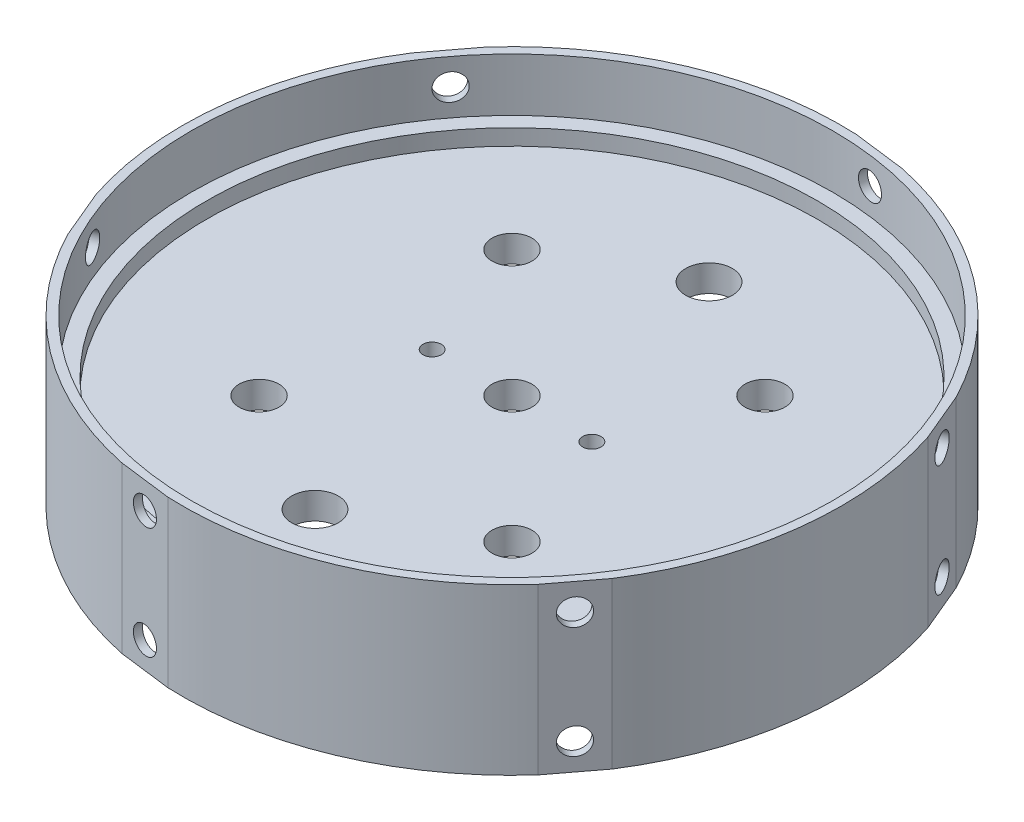
SolidWorks part; units mm, degrees
material "6061-T6 (SS)"
ref_plane "Front Plane" through (0, 0, 0) normal (0, 0, 1) x (1, 0, 0)
ref_plane "Top Plane" through (0, 0, 0) normal (0, 1, 0) x (1, 0, 0)
ref_plane "Right Plane" through (0, 0, 0) normal (1, 0, 0) x (0, 0, -1)
ref_axis "Axis1" through (0, 55, 0) along (0, -1, 0)
sketch "Sketch3" plane through (0, 0, 0) normal (0, 1, 0) x (1, 0, 0)
  circle A0 centre (0, 0) radius 78.5876
  dimension "D1" = 157.1752
extrude "Boss-Extrude1" add sketch "Sketch3" along normal blind 3.175 and the other way blind 3.175
sketch "Sketch4" plane through (0, 3.175, 0) normal (0, 1, 0) x (1, 0, 0)
  circle A0 centre (0, 0) radius 78.5876
  circle A1 centre (0, 0) radius 72.8662
  dimension "D1" = 157.1752
  dimension "D2" = 145.7325
extrude "Boss-Extrude3" add sketch "Sketch4" along normal blind 3.81
sketch "Sketch6" plane through (0, 6.985, 0) normal (0, 1, 0) x (1, 0, 0)
  circle A0 centre (0, 0) radius 78.5876
  circle A1 centre (0, 0) radius 76.454
  dimension "D1" = 157.1752
  dimension "D2" = 152.908
extrude "Boss-Extrude4" add sketch "Sketch6" along normal blind 12.7
hole_wizard "1/4 (0.25) Diameter Hole2" positions "3DSketch2" profile "Sketch7" hole size "1/4" standard "ANSI Inch" end condition up to next
sketch3d "3DSketch2"
  point P0 (-9.8633, 13.335, 77.9662)
  dimension "D1" = 6.35
sketch "Sketch7" plane through (-9.8633, 13.335, 77.9662) normal (0, 1, 0) x (0.9921, 0, 0.1255)
  line L0 (0, 0) -> (0, 185.7135)
  line L1 (0, 185.7135) -> (3.175, 185.7135)
  line L2 (3.175, 185.7135) -> (3.175, 0)
  line L5 (3.175, 0) -> (0, 0)
  line L11 (0, -6.35) -> (0, 107.95) construction
  dimension "Thru Hole Dia." = 6.35
  dimension "Thru Hole Depth" = 185.7135
pattern_circular "CirPattern2" count 6 over 360 about axis through (0, 55, 0) along (0, -1, 0) of "1/4 (0.25) Diameter Hole2"
mirror "Mirror3" about plane through (0, 0, 0) normal (0, 1, 0) of "Boss-Extrude3", "Boss-Extrude4", "1/4 (0.25) Diameter Hole2", "CirPattern2"
hole_wizard "3/8 (0.375) Diameter Hole1" positions "Sketch8" profile "Sketch9" hole size "3/8" standard "ANSI Inch" end condition up to next
sketch "Sketch8" plane through (0, 3.175, 0) normal (0, 1, 0) x (1, 0, 0)
  line L0 (-30.1625, 30.1625) -> (30.1625, -30.1625) construction
  point P0 (-30.1625, 30.1625)
  point P2 (30.1625, 30.1625)
  point P4 (30.1625, -30.1625)
  point P6 (-30.1625, -30.1625)
  point P17 (0, 0)
  dimension "D1" = 60.325
  dimension "D2" = 60.325
sketch "Sketch9" plane through (-30.1625, 3.175, -30.1625) normal (1, 0, 0) x (0, 0, 1)
  line L0 (0, 0) -> (0, 6.35)
  line L1 (0, 6.35) -> (4.7625, 6.35)
  line L2 (4.7625, 6.35) -> (4.7625, 0)
  line L5 (4.7625, 0) -> (0, 0)
  line L11 (0, -6.35) -> (0, 107.95) construction
  dimension "Thru Hole Dia." = 9.525
  dimension "Thru Hole Depth" = 6.35
ref_axis "Axis2" through (-9.5696, 13.335, 75.645) along (-0.1255, 0, 0.9921)
ref_plane "Plane1" through (-9.8633, 0, 77.9662) normal (-0.1255, 0, 0.9921) x (0.9921, 0, 0.1255)
sketch "Sketch11" plane through (-9.8633, 0, 77.9662) normal (-0.1255, 0, 0.9921) x (0.9921, 0, 0.1255)
  line L1 (-20.18, 23.5914) -> (21.0466, 23.5914)
  line L2 (-20.18, 23.5914) -> (-20.18, -28.7325)
  line L3 (-20.18, -28.7325) -> (21.0466, -28.7325)
  line L4 (21.0466, 23.5914) -> (21.0466, -28.7325)
extrude "Cut-Extrude2" cut sketch "Sketch11" against normal blind 0.254
pattern_circular "CirPattern4" count 6 over 360 about axis through (0, 55, 0) along (0, -1, 0) of "Cut-Extrude2"
hole_wizard "3/8 (0.375) Diameter Hole2" positions "Sketch12" profile "Sketch13" hole size "3/8" standard "ANSI Inch" end condition up to next
sketch "Sketch12" plane through (0, 3.175, 0) normal (0, 1, 0) x (1, 0, 0)
  point P0 (0, 0)
sketch "Sketch13" plane through (0, 3.175, 0) normal (1, 0, 0) x (0, 0, 1)
  line L0 (0, 0) -> (0, 6.35)
  line L1 (0, 6.35) -> (4.7625, 6.35)
  line L2 (4.7625, 6.35) -> (4.7625, 0)
  line L5 (4.7625, 0) -> (0, 0)
  line L11 (0, -6.35) -> (0, 107.95) construction
  dimension "Thru Hole Dia." = 9.525
  dimension "Thru Hole Depth" = 6.35
hole_wizard "7/16 (0.4375) Diameter Hole1" positions "Sketch14" profile "Sketch15" hole size "7/16" standard "ANSI Inch" end condition up to next
sketch "Sketch14" plane through (0, 3.175, 0) normal (0, 1, 0) x (1, 0, 0)
  line L2 (0, -21.6535) -> (0, 21.6535) construction
  line L3 (0, -46.99) -> (0, 46.99) construction
  point P0 (0, -46.99)
  point P2 (0, 46.99)
  point P29 (0, 0)
  dimension "D1" = 93.98
sketch "Sketch15" plane through (0, 3.175, 46.99) normal (1, 0, 0) x (0, 0, 1)
  line L0 (0, 0) -> (0, 6.35)
  line L1 (0, 6.35) -> (5.5562, 6.35)
  line L2 (5.5562, 6.35) -> (5.5562, 0)
  line L5 (5.5562, 0) -> (0, 0)
  line L11 (0, -6.35) -> (0, 107.95) construction
  dimension "Thru Hole Dia." = 11.1125
  dimension "Thru Hole Depth" = 6.35
hole_wizard "11/64 (0.17188) Diameter Hole1" positions "Sketch16" profile "Sketch17" hole size "11/64" standard "ANSI Inch" end condition up to next
sketch "Sketch16" plane through (0, 3.175, 0) normal (0, 1, 0) x (1, 0, 0)
  line L0 (19.05, 0) -> (-19.05, 0) construction
  point P0 (-19.05, 0)
  point P2 (19.05, 0)
  point P11 (0, 0)
  point P13 (29.079, 0)
  dimension "D1" = 38.1
sketch "Sketch17" plane through (-19.05, 3.175, 0) normal (1, 0, 0) x (0, 0, 1)
  line L0 (0, 0) -> (0, 6.35)
  line L1 (0, 6.35) -> (2.1829, 6.35)
  line L2 (2.1829, 6.35) -> (2.1829, 0)
  line L5 (2.1829, 0) -> (0, 0)
  line L11 (0, -6.35) -> (0, 107.95) construction
  dimension "Thru Hole Dia." = 4.3658
  dimension "Thru Hole Depth" = 6.35
